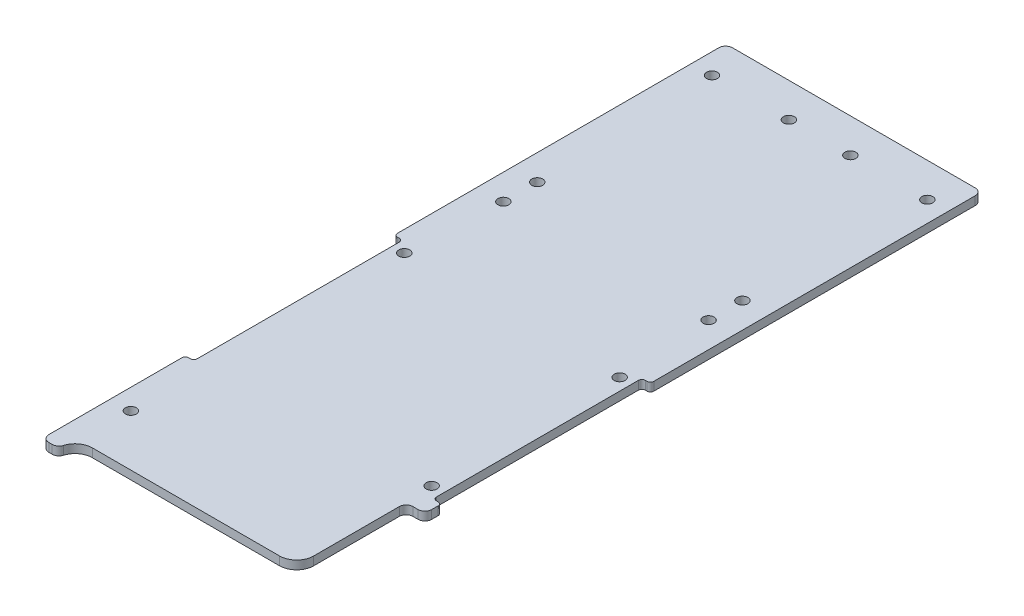
SolidWorks part; units mm, degrees
ref_plane "Front Plane" through (0, 0, 0) normal (0, 0, 1) x (1, 0, 0)
ref_plane "Top Plane" through (0, 0, 0) normal (0, 1, 0) x (1, 0, 0)
ref_plane "Right Plane" through (0, 0, 0) normal (1, 0, 0) x (0, 0, -1)
sketch "Sketch1" plane through (0, 0, 0) normal (0, 1, 0) x (1, 0, 0)
  line L0 (-39.9997, 0) -> (-39.9997, 114.3) construction
  line L1 (-47.625, 127) -> (47.625, 127)
  line L2 (-47.625, 127) -> (-47.625, -127)
  line L3 (-47.625, -127) -> (47.625, -127)
  line L4 (47.625, 127) -> (47.625, -127)
  line L5 (-47.625, 127) -> (47.625, -127) construction
  line L6 (-47.625, -127) -> (47.625, 127) construction
  line L7 (0, 0) -> (0, 127) construction
  line L8 (-39.9997, 0) -> (-39.9997, -101.6) construction
  line L9 (-39.9997, 0) -> (0, 0) construction
  line L10 (-41.275, -127) -> (-41.275, -120.65)
  line L11 (-41.275, -120.65) -> (41.275, -120.65)
  line L12 (41.275, -120.65) -> (41.275, -127)
  line L13 (-39.9997, 114.3) -> (-11.4247, 114.3) construction
  line L14 (39.9997, 114.3) -> (11.4247, 114.3) construction
  circle A0 centre (-39.9997, 114.3) radius 2.032
  circle A1 centre (-39.9997, 0) radius 2.032
  circle A2 centre (-39.9997, -101.6) radius 2.032
  circle A3 centre (39.9997, -101.6) radius 2.032
  circle A4 centre (39.9997, 0) radius 2.032
  circle A5 centre (39.9997, 114.3) radius 2.032
  circle A6 centre (-11.4247, 114.3) radius 2.032
  circle A7 centre (11.4247, 114.3) radius 2.032
  circle A8 centre (-39.9997, -69.85) radius 2.032
  circle A9 centre (39.9997, -69.85) radius 2.032
  point P0 (0, 0)
  dimension "D4" = 4.064
  dimension "D10" = 28.575
  dimension "D1" = 95.25
  dimension "D2" = 254
  dimension "D3" = 7.6253
  dimension "D5" = 12.7
  dimension "D6" = 25.4
  dimension "D7" = 6.35
  dimension "D8" = 6.35
  dimension "D9" = 6.35
  dimension "D11" = 69.85
extrude "Boss-Extrude1" add sketch "Sketch1" along normal blind 3.175 contours L4 L1 L2 L3 A4 A0 A1 A2 A3 A5 | A8 | A3 region at (0, 0, -2.6944) region at (39.9997, 0, 101.6) region at (-39.9997, 0, 69.85)
fillet "Fillet1" radius 2.54 4 edges at (-47.625, 1.5875, -127) (47.625, 1.5875, -127) (47.625, 1.5875, 127) (-47.625, 1.5875, 127)
fillet "Fillet2" radius 2.54 2 edges at (41.275, 1.5875, 127) (-41.275, 1.5875, 127)
fillet "Fillet3" radius 6.35 2 edges at (41.275, 1.5875, 120.65) (-41.275, 1.5875, 120.65)
sketch "Sketch2" plane through (0, 0, 0) normal (0, -1, 0) x (1, 0, 0)
  line L0 (41.9124, 131.8831) -> (41.9124, 109.8659) construction
  line L1 (41.9124, 109.8659) -> (41.9124, 106.3879) construction
  line L2 (41.9124, 83.271) -> (41.9124, 82.5325) construction
  line L3 (41.9124, 82.5325) -> (41.9124, 81.2514) construction
  line L4 (41.9124, 83.271) -> (41.9124, 106.3879) construction
  line L5 (41.9124, 131.8831) -> (41.9124, 109.8659)
  line L6 (41.9124, 109.8659) -> (41.9124, 106.3879)
  line L7 (41.9124, 83.271) -> (41.9124, 82.5325)
  line L8 (41.9124, 82.5325) -> (41.9124, 81.2514)
  line L9 (41.9124, 83.271) -> (41.9124, 106.3879)
  line L10 (41.9124, 81.2514) -> (47.625, 81.2514)
  line L11 (47.625, -124.46) -> (47.625, 124.46) construction
  line L12 (41.9124, 131.8831) -> (47.625, 131.8831)
  line L13 (47.625, 131.8831) -> (47.625, 81.2514)
  line L14 (40.6424, 79.9814) -> (48.895, 79.9814)
  line L15 (48.895, 133.1531) -> (48.895, 79.9814)
  line L16 (40.6424, 133.1531) -> (48.895, 133.1531)
  line L17 (40.6424, 133.1531) -> (40.6424, 109.8659)
  line L18 (40.6424, 109.8659) -> (40.6424, 106.3879)
  line L19 (40.6424, 83.271) -> (40.6424, 106.3879)
  line L20 (40.6424, 83.271) -> (40.6424, 82.5325)
  line L21 (40.6424, 82.5325) -> (40.6424, 79.9814)
  arc M7 (43.815, 127) -> (41.3809, 125.1857) centre (43.815, 124.46) ccw
  arc M8 (41.3809, 125.1857) -> (35.2956, 120.65) centre (35.2956, 127) cw
  line M18 (47.625, -124.46) -> (47.625, 124.46)
  dimension "D1" = 1.27
extrude "Cut-Extrude1" cut sketch "Sketch2" against normal through all contours L20 L21 L14 L10 L8 L7 L9 L19 M18 | L19 L9 L6 L5 L17 L18 M7 M8 | L13 L10 L8 L7 L9 L6 L5 L12 region at (41.6773, 0, 99.982)
fillet "Fillet4" radius 6.35 1 edges at (40.6424, 1.5875, 123.5744)
fillet "Fillet5" radius 2.54 2 edges at (47.625, 1.5875, 79.9814) (40.6424, 1.5875, 79.9814)
sketch "Sketch3" plane through (0, 0, 0) normal (0, -1, 0) x (1, 0, 0)
  line L0 (-36.3082, -49.7791) -> (-39.915, -49.7791) construction
  line L1 (-40.423, -49.276) -> (-40.423, -45.7043) construction
  line L2 (-35.8002, -45.7043) -> (-35.8002, -49.276) construction
  line L3 (-39.915, -45.2013) -> (-36.3082, -45.2013) construction
  line L4 (-36.3082, -37.2027) -> (-39.915, -37.2027) construction
  line L5 (-35.8002, -33.1279) -> (-35.8002, -36.6996) construction
  line L6 (-40.423, -36.6996) -> (-40.423, -33.1279) construction
  line L7 (-39.915, -32.6249) -> (-36.3082, -32.6249) construction
  line L8 (36.285, -32.6249) -> (39.8918, -32.6249) construction
  line L9 (40.3998, -33.1279) -> (40.3998, -36.6996) construction
  line L10 (39.8918, -37.2027) -> (36.285, -37.2027) construction
  line L11 (35.777, -36.6996) -> (35.777, -33.1279) construction
  line L12 (36.285, -45.2013) -> (39.8918, -45.2013) construction
  line L13 (35.777, -49.276) -> (35.777, -45.7043) construction
  line L14 (40.3998, -45.7043) -> (40.3998, -49.276) construction
  line L15 (39.8918, -49.7791) -> (36.285, -49.7791) construction
  line L16 (-36.3082, -49.7791) -> (-39.915, -49.7791)
  line L17 (-40.423, -49.276) -> (-40.423, -45.7043)
  line L18 (-35.8002, -45.7043) -> (-35.8002, -49.276)
  line L19 (-39.915, -45.2013) -> (-36.3082, -45.2013)
  line L20 (-36.3082, -37.2027) -> (-39.915, -37.2027)
  line L21 (-35.8002, -33.1279) -> (-35.8002, -36.6996)
  line L22 (-40.423, -36.6996) -> (-40.423, -33.1279)
  line L23 (-39.915, -32.6249) -> (-36.3082, -32.6249)
  line L24 (36.285, -32.6249) -> (39.8918, -32.6249)
  line L25 (40.3998, -33.1279) -> (40.3998, -36.6996)
  line L26 (39.8918, -37.2027) -> (36.285, -37.2027)
  line L27 (35.777, -36.6996) -> (35.777, -33.1279)
  line L28 (36.285, -45.2013) -> (39.8918, -45.2013)
  line L29 (35.777, -49.276) -> (35.777, -45.7043)
  line L30 (40.3998, -45.7043) -> (40.3998, -49.276)
  line L31 (39.8918, -49.7791) -> (36.285, -49.7791)
  line L32 (-47.625, -25.836) -> (47.625, -25.836)
  line L33 (-47.625, -124.46) -> (-47.625, 124.46) construction
  line L34 (47.625, -124.46) -> (47.625, 77.4414) construction
  line L35 (0, -25.836) -> (0, -56.0686) construction
  line L38 (134.3626, -51.414) -> (184.1384, -51.414)
  line L39 (184.1384, -51.414) -> (184.1384, -43.4909)
  line L40 (184.1384, -43.4909) -> (182.335, -43.4909)
  line L41 (181.827, -42.9878) -> (181.827, -39.4161)
  line L42 (182.335, -38.9131) -> (184.1384, -38.9131)
  line L43 (184.1384, -38.9131) -> (184.1384, -30.9899)
  line L44 (184.1384, -30.9899) -> (134.3626, -30.9899)
  line L45 (134.3626, -30.9899) -> (133.3384, -32.0042)
  line L46 (133.3384, -32.0042) -> (132.3143, -30.9899)
  line L47 (132.3143, -30.9899) -> (70.8626, -30.9899)
  line L48 (70.8626, -30.9899) -> (69.8384, -32.0042)
  line L49 (69.8384, -32.0042) -> (68.8143, -30.9899)
  line L50 (68.8143, -30.9899) -> (7.3626, -30.9899)
  line L51 (7.3626, -30.9899) -> (6.3384, -32.0042)
  line L52 (6.3384, -32.0042) -> (5.3143, -30.9899)
  line L53 (5.3143, -30.9899) -> (-56.1374, -30.9899)
  line L54 (-56.1374, -30.9899) -> (-57.1616, -32.0042)
  line L55 (-57.1616, -32.0042) -> (-58.1857, -30.9899)
  line L56 (-58.1857, -30.9899) -> (-119.6374, -30.9899)
  line L57 (-119.6374, -30.9899) -> (-120.6616, -32.0042)
  line L58 (-120.6616, -32.0042) -> (-121.6857, -30.9899)
  line L59 (-121.6857, -30.9899) -> (-184.1616, -30.9899)
  line L60 (-184.1616, -30.9899) -> (-184.1616, -51.414)
  line L61 (-184.1616, -51.414) -> (-121.6857, -51.414)
  line L62 (-121.6857, -51.414) -> (-120.6616, -50.3998)
  line L63 (-120.6616, -50.3998) -> (-119.6374, -51.414)
  line L64 (-119.6374, -51.414) -> (-58.1857, -51.414)
  line L65 (-58.1857, -51.414) -> (-57.1616, -50.3998)
  line L66 (-57.1616, -50.3998) -> (-56.1374, -51.414)
  line L67 (-56.1374, -51.414) -> (5.3143, -51.414)
  line L68 (5.3143, -51.414) -> (6.3384, -50.3998)
  line L69 (6.3384, -50.3998) -> (7.3626, -51.414)
  line L70 (7.3626, -51.414) -> (68.8143, -51.414)
  line L71 (68.8143, -51.414) -> (69.8384, -50.3998)
  line L72 (69.8384, -50.3998) -> (70.8626, -51.414)
  line L73 (70.8626, -51.414) -> (132.3143, -51.414)
  line L74 (132.3143, -51.414) -> (133.3384, -50.3998)
  line L75 (133.3384, -50.3998) -> (134.3626, -51.414)
  line L76 (134.3626, -51.414) -> (184.1384, -51.414)
  line L77 (184.1384, -51.414) -> (184.1384, -43.4909)
  line L78 (184.1384, -43.4909) -> (182.335, -43.4909)
  line L79 (181.827, -42.9878) -> (181.827, -39.4161)
  line L80 (182.335, -38.9131) -> (184.1384, -38.9131)
  line L81 (184.1384, -38.9131) -> (184.1384, -30.9899)
  line L82 (184.1384, -30.9899) -> (134.3626, -30.9899)
  line L83 (134.3626, -30.9899) -> (133.3384, -32.0042)
  line L84 (133.3384, -32.0042) -> (132.3143, -30.9899)
  line L85 (132.3143, -30.9899) -> (70.8626, -30.9899)
  line L86 (70.8626, -30.9899) -> (69.8384, -32.0042)
  line L87 (69.8384, -32.0042) -> (68.8143, -30.9899)
  line L88 (68.8143, -30.9899) -> (7.3626, -30.9899)
  line L89 (7.3626, -30.9899) -> (6.3384, -32.0042)
  line L90 (6.3384, -32.0042) -> (5.3143, -30.9899)
  line L91 (5.3143, -30.9899) -> (-56.1374, -30.9899)
  line L92 (-56.1374, -30.9899) -> (-57.1616, -32.0042)
  line L93 (-57.1616, -32.0042) -> (-58.1857, -30.9899)
  line L94 (-58.1857, -30.9899) -> (-119.6374, -30.9899)
  line L95 (-119.6374, -30.9899) -> (-120.6616, -32.0042)
  line L96 (-120.6616, -32.0042) -> (-121.6857, -30.9899)
  line L97 (-121.6857, -30.9899) -> (-184.1616, -30.9899)
  line L98 (-184.1616, -30.9899) -> (-184.1616, -51.414)
  line L99 (-184.1616, -51.414) -> (-121.6857, -51.414)
  line L100 (-121.6857, -51.414) -> (-120.6616, -50.3998)
  line L101 (-120.6616, -50.3998) -> (-119.6374, -51.414)
  line L102 (-119.6374, -51.414) -> (-58.1857, -51.414)
  line L103 (-58.1857, -51.414) -> (-57.1616, -50.3998)
  line L104 (-57.1616, -50.3998) -> (-56.1374, -51.414)
  line L105 (-56.1374, -51.414) -> (5.3143, -51.414)
  line L106 (5.3143, -51.414) -> (6.3384, -50.3998)
  line L107 (6.3384, -50.3998) -> (7.3626, -51.414)
  line L108 (7.3626, -51.414) -> (68.8143, -51.414)
  line L109 (68.8143, -51.414) -> (69.8384, -50.3998)
  line L110 (69.8384, -50.3998) -> (70.8626, -51.414)
  line L111 (70.8626, -51.414) -> (132.3143, -51.414)
  line L112 (132.3143, -51.414) -> (133.3384, -50.3998)
  line L113 (133.3384, -50.3998) -> (134.3626, -51.414)
  line L1362 (-40.423, -34.9138) -> (-35.8002, -34.9138)
  line L1857 (-38.1116, -32.6249) -> (-38.1116, -37.2027)
  line L1858 (-38.1116, -45.2013) -> (-38.1116, -49.7791)
  line L1859 (-40.423, -47.4902) -> (-35.8002, -47.4902)
  circle A0 centre (-38.1116, -34.9138) radius 2.032
  circle A1 centre (-38.1116, -47.4902) radius 2.032
  circle A2 centre (38.1116, -47.4902) radius 2.032
  circle A3 centre (38.1116, -34.9138) radius 2.032
  ellipse E0 centre (-39.915, -45.7043) end of major axis (-39.407, -45.7043) minor radius 0.5031 (-39.915, -45.2013) -> (-40.423, -45.7043) ccw construction
  ellipse E1 centre (-39.915, -49.276) end of major axis (-39.407, -49.276) minor radius 0.5031 (-40.423, -49.276) -> (-39.915, -49.7791) ccw construction
  ellipse E2 centre (182.335, -42.9878) end of major axis (182.843, -42.9878) minor radius 0.5031 (181.827, -42.9878) -> (182.335, -43.4909) ccw
  ellipse E3 centre (182.335, -39.4161) end of major axis (182.843, -39.4161) minor radius 0.5031 (182.335, -38.9131) -> (181.827, -39.4161) ccw
  ellipse E4 centre (182.335, -42.9878) end of major axis (182.843, -42.9878) minor radius 0.5031 (181.827, -42.9878) -> (182.335, -43.4909) ccw
  ellipse E5 centre (182.335, -39.4161) end of major axis (182.843, -39.4161) minor radius 0.5031 (182.335, -38.9131) -> (181.827, -39.4161) ccw
  ellipse E6 centre (-36.3082, -49.276) end of major axis (-35.8002, -49.276) minor radius 0.5031 (-36.3082, -49.7791) -> (-35.8002, -49.276) ccw construction
  ellipse E7 centre (-36.3082, -45.7043) end of major axis (-35.8002, -45.7043) minor radius 0.5031 (-35.8002, -45.7043) -> (-36.3082, -45.2013) ccw construction
  ellipse E8 centre (-39.915, -36.6996) end of major axis (-39.407, -36.6996) minor radius 0.5031 (-40.423, -36.6996) -> (-39.915, -37.2027) ccw construction
  ellipse E9 centre (-36.3082, -36.6996) end of major axis (-35.8002, -36.6996) minor radius 0.5031 (-36.3082, -37.2027) -> (-35.8002, -36.6996) ccw construction
  ellipse E10 centre (-36.3082, -33.1279) end of major axis (-35.8002, -33.1279) minor radius 0.5031 (-35.8002, -33.1279) -> (-36.3082, -32.6249) ccw construction
  ellipse E11 centre (-39.915, -33.1279) end of major axis (-39.407, -33.1279) minor radius 0.5031 (-39.915, -32.6249) -> (-40.423, -33.1279) ccw construction
  ellipse E12 centre (39.8918, -33.1279) end of major axis (40.3998, -33.1279) minor radius 0.5031 (40.3998, -33.1279) -> (39.8918, -32.6249) ccw construction
  ellipse E13 centre (36.285, -33.1279) end of major axis (36.793, -33.1279) minor radius 0.5031 (36.285, -32.6249) -> (35.777, -33.1279) ccw construction
  ellipse E14 centre (39.8918, -36.6996) end of major axis (40.3998, -36.6996) minor radius 0.5031 (39.8918, -37.2027) -> (40.3998, -36.6996) ccw construction
  ellipse E15 centre (36.285, -36.6996) end of major axis (36.793, -36.6996) minor radius 0.5031 (35.777, -36.6996) -> (36.285, -37.2027) ccw construction
  ellipse E16 centre (36.285, -45.7043) end of major axis (36.793, -45.7043) minor radius 0.5031 (36.285, -45.2013) -> (35.777, -45.7043) ccw construction
  ellipse E17 centre (36.285, -49.276) end of major axis (36.793, -49.276) minor radius 0.5031 (35.777, -49.276) -> (36.285, -49.7791) ccw construction
  ellipse E18 centre (39.8918, -45.7043) end of major axis (40.3998, -45.7043) minor radius 0.5031 (40.3998, -45.7043) -> (39.8918, -45.2013) ccw construction
  ellipse E19 centre (39.8918, -49.276) end of major axis (40.3998, -49.276) minor radius 0.5031 (39.8918, -49.7791) -> (40.3998, -49.276) ccw construction
  ellipse E20 centre (-39.915, -45.7043) end of major axis (-39.407, -45.7043) minor radius 0.5031 (-39.915, -45.2013) -> (-40.423, -45.7043) ccw
  ellipse E21 centre (-39.915, -49.276) end of major axis (-39.407, -49.276) minor radius 0.5031 (-40.423, -49.276) -> (-39.915, -49.7791) ccw
  ellipse E22 centre (-36.3082, -49.276) end of major axis (-35.8002, -49.276) minor radius 0.5031 (-36.3082, -49.7791) -> (-35.8002, -49.276) ccw
  ellipse E23 centre (-36.3082, -45.7043) end of major axis (-35.8002, -45.7043) minor radius 0.5031 (-35.8002, -45.7043) -> (-36.3082, -45.2013) ccw
  ellipse E24 centre (-39.915, -36.6996) end of major axis (-39.407, -36.6996) minor radius 0.5031 (-40.423, -36.6996) -> (-39.915, -37.2027) ccw
  ellipse E25 centre (-36.3082, -36.6996) end of major axis (-35.8002, -36.6996) minor radius 0.5031 (-36.3082, -37.2027) -> (-35.8002, -36.6996) ccw
  ellipse E26 centre (-36.3082, -33.1279) end of major axis (-35.8002, -33.1279) minor radius 0.5031 (-35.8002, -33.1279) -> (-36.3082, -32.6249) ccw
  ellipse E27 centre (-39.915, -33.1279) end of major axis (-39.407, -33.1279) minor radius 0.5031 (-39.915, -32.6249) -> (-40.423, -33.1279) ccw
  ellipse E28 centre (39.8918, -33.1279) end of major axis (40.3998, -33.1279) minor radius 0.5031 (40.3998, -33.1279) -> (39.8918, -32.6249) ccw
  ellipse E29 centre (36.285, -33.1279) end of major axis (36.793, -33.1279) minor radius 0.5031 (36.285, -32.6249) -> (35.777, -33.1279) ccw
  ellipse E30 centre (39.8918, -36.6996) end of major axis (40.3998, -36.6996) minor radius 0.5031 (39.8918, -37.2027) -> (40.3998, -36.6996) ccw
  ellipse E31 centre (36.285, -36.6996) end of major axis (36.793, -36.6996) minor radius 0.5031 (35.777, -36.6996) -> (36.285, -37.2027) ccw
  ellipse E32 centre (36.285, -45.7043) end of major axis (36.793, -45.7043) minor radius 0.5031 (36.285, -45.2013) -> (35.777, -45.7043) ccw
  ellipse E33 centre (36.285, -49.276) end of major axis (36.793, -49.276) minor radius 0.5031 (35.777, -49.276) -> (36.285, -49.7791) ccw
  ellipse E34 centre (39.8918, -45.7043) end of major axis (40.3998, -45.7043) minor radius 0.5031 (40.3998, -45.7043) -> (39.8918, -45.2013) ccw
  ellipse E35 centre (39.8918, -49.276) end of major axis (40.3998, -49.276) minor radius 0.5031 (39.8918, -49.7791) -> (40.3998, -49.276) ccw
  dimension "D2" = 4.064
  dimension "D1" = 0
extrude "Cut-Extrude2" cut sketch "Sketch3" against normal through all contours A0 | A1 | A2 | A3
sketch "Sketch4" plane through (0, 3.175, 0) normal (0, 1, 0) x (1, 0, 0)
  line L0 (-44.45, 3.81) -> (-46.99, 3.81) construction
  line L1 (-46.99, 3.81) -> (-46.99, 121.92) construction
  line L2 (-42.545, 126.365) -> (-0.635, 126.365) construction
  line L3 (-0.635, 126.365) -> (-0.635, 107.95) construction
  line L4 (-6.35, 102.235) -> (-15.875, 102.235) construction
  line L5 (-22.86, 95.25) -> (-22.86, -115.57) construction
  line L6 (-27.305, -120.015) -> (-35.4551, -120.015) construction
  line L7 (-43.815, -126.365) -> (-45.085, -126.365) construction
  line L8 (-46.99, -124.46) -> (-46.99, -73.7819) construction
  line L9 (-46.99, -73.7819) -> (-44.45, -73.7819) construction
  line L10 (-44.45, -73.7819) -> (-44.45, 3.81) construction
  line L11 (-46.99, 3.81) -> (-44.45, 3.81)
  line L12 (-46.99, 121.92) -> (-46.99, 3.81)
  line L13 (-0.635, 126.365) -> (-42.545, 126.365)
  line L14 (-0.635, 107.95) -> (-0.635, 126.365)
  line L15 (-15.875, 102.235) -> (-6.35, 102.235)
  line L16 (-22.86, -115.57) -> (-22.86, 95.25)
  line L17 (-35.4551, -120.015) -> (-27.305, -120.015)
  line L18 (-45.085, -126.365) -> (-43.815, -126.365)
  line L19 (-46.99, -73.7819) -> (-46.99, -124.46)
  line L20 (-44.45, -73.7819) -> (-46.99, -73.7819)
  line L21 (-44.45, 3.81) -> (-44.45, -73.7819)
  line L22 (-46.99, 3.81) -> (-44.45, 3.81)
  line L23 (-46.99, 121.92) -> (-46.99, 3.81)
  line L24 (-0.635, 126.365) -> (-42.545, 126.365)
  line L25 (-0.635, 107.95) -> (-0.635, 126.365)
  line L26 (-15.875, 102.235) -> (-6.35, 102.235)
  line L27 (-22.86, -115.57) -> (-22.86, 95.25)
  line L28 (-35.4551, -120.015) -> (-27.305, -120.015)
  line L29 (-45.085, -126.365) -> (-43.815, -126.365)
  line L30 (-46.99, -73.7819) -> (-46.99, -124.46)
  line L31 (-44.45, -73.7819) -> (-46.99, -73.7819)
  line L32 (-44.45, 3.81) -> (-44.45, -73.7819)
  line L33 (40.64, -77.5286) -> (40.64, -117.0408) construction
  line L34 (35.4551, -120.015) -> (27.305, -120.015) construction
  line L35 (22.86, -115.57) -> (22.86, 95.25) construction
  line L36 (15.875, 102.235) -> (6.35, 102.235) construction
  line L37 (0.635, 107.95) -> (0.635, 126.365) construction
  line L38 (0.635, 126.365) -> (42.545, 126.365) construction
  line L39 (46.99, 121.92) -> (46.99, 3.81) construction
  line L40 (46.99, 3.81) -> (44.45, 3.81) construction
  line L41 (44.45, 3.81) -> (44.45, -73.7819) construction
  line L42 (44.45, -73.7819) -> (46.99, -73.7819) construction
  line L43 (46.99, -73.7819) -> (46.99, -77.5286) construction
  line L44 (46.99, -77.5286) -> (40.64, -77.5286) construction
  line L45 (-44.45, 3.81) -> (-46.99, 3.81)
  line L46 (-46.99, 3.81) -> (-46.99, 121.92)
  line L47 (-42.545, 126.365) -> (-0.635, 126.365)
  line L48 (-0.635, 126.365) -> (-0.635, 107.95)
  line L49 (-6.35, 102.235) -> (-15.875, 102.235)
  line L50 (-22.86, 95.25) -> (-22.86, -115.57)
  line L51 (-27.305, -120.015) -> (-35.4551, -120.015)
  line L52 (-43.815, -126.365) -> (-45.085, -126.365)
  line L53 (-46.99, -124.46) -> (-46.99, -73.7819)
  line L54 (-46.99, -73.7819) -> (-44.45, -73.7819)
  line L55 (-44.45, -73.7819) -> (-44.45, 3.81)
  line L56 (40.64, -77.5286) -> (40.64, -117.0408)
  line L57 (35.4551, -120.015) -> (27.305, -120.015)
  line L58 (22.86, -115.57) -> (22.86, 95.25)
  line L59 (15.875, 102.235) -> (6.35, 102.235)
  line L60 (0.635, 107.95) -> (0.635, 126.365)
  line L61 (0.635, 126.365) -> (42.545, 126.365)
  line L62 (46.99, 121.92) -> (46.99, 3.81)
  line L63 (46.99, 3.81) -> (44.45, 3.81)
  line L64 (44.45, 3.81) -> (44.45, -73.7819)
  line L65 (44.45, -73.7819) -> (46.99, -73.7819)
  line L66 (46.99, -73.7819) -> (46.99, -77.5286)
  line L67 (46.99, -77.5286) -> (40.64, -77.5286)
  line L178 (-46.99, 3.81) -> (-47.625, 3.81)
  line L179 (-47.625, 124.46) -> (-47.625, -124.46) construction
  line L180 (-46.99, -73.7819) -> (-47.625, -73.7819)
  line L181 (46.99, -73.7819) -> (47.625, -73.7819)
  line L182 (47.625, 124.46) -> (47.625, -77.4414) construction
  line L183 (46.99, 3.81) -> (47.625, 3.81)
  arc A0 (-42.545, 126.365) -> (-46.99, 121.92) centre (-42.545, 121.92) ccw construction
  arc A1 (-6.35, 102.235) -> (-0.635, 107.95) centre (-6.35, 107.95) ccw construction
  arc A2 (-15.875, 102.235) -> (-22.86, 95.25) centre (-15.875, 95.25) ccw construction
  arc A3 (-27.305, -120.015) -> (-22.86, -115.57) centre (-27.305, -115.57) ccw construction
  arc A4 (-35.4551, -120.015) -> (-41.9138, -124.3399) centre (-35.4551, -127) ccw construction
  arc A5 (-43.815, -126.365) -> (-41.9138, -124.3399) centre (-43.815, -124.46) ccw construction
  arc A6 (-46.99, -124.46) -> (-45.085, -126.365) centre (-45.085, -124.46) ccw construction
  arc A7 (-42.545, 126.365) -> (-46.99, 121.92) centre (-42.545, 121.92) ccw
  arc A8 (-6.35, 102.235) -> (-0.635, 107.95) centre (-6.35, 107.95) ccw
  arc A9 (-15.875, 102.235) -> (-22.86, 95.25) centre (-15.875, 95.25) ccw
  arc A10 (-27.305, -120.015) -> (-22.86, -115.57) centre (-27.305, -115.57) ccw
  arc A11 (-35.4551, -120.015) -> (-41.9138, -124.3399) centre (-35.4551, -127) ccw
  arc A12 (-43.815, -126.365) -> (-41.9138, -124.3399) centre (-43.815, -124.46) ccw
  arc A13 (-46.99, -124.46) -> (-45.085, -126.365) centre (-45.085, -124.46) ccw
  arc A14 (-42.545, 126.365) -> (-46.99, 121.92) centre (-42.545, 121.92) ccw
  arc A15 (-6.35, 102.235) -> (-0.635, 107.95) centre (-6.35, 107.95) ccw
  arc A16 (-15.875, 102.235) -> (-22.86, 95.25) centre (-15.875, 95.25) ccw
  arc A17 (-27.305, -120.015) -> (-22.86, -115.57) centre (-27.305, -115.57) ccw
  arc A18 (-35.4551, -120.015) -> (-41.9138, -124.3399) centre (-35.4551, -127) ccw
  arc A19 (-43.815, -126.365) -> (-41.9138, -124.3399) centre (-43.815, -124.46) ccw
  arc A20 (-46.99, -124.46) -> (-45.085, -126.365) centre (-45.085, -124.46) ccw
  arc A21 (36.8369, -120.153) -> (40.64, -117.0408) centre (37.465, -117.0408) ccw construction
  arc A22 (36.8369, -120.153) -> (35.4551, -120.015) centre (35.4551, -127) ccw construction
  arc A23 (22.86, -115.57) -> (27.305, -120.015) centre (27.305, -115.57) ccw construction
  arc A24 (22.86, 95.25) -> (15.875, 102.235) centre (15.875, 95.25) ccw construction
  arc A25 (0.635, 107.95) -> (6.35, 102.235) centre (6.35, 107.95) ccw construction
  arc A26 (46.99, 121.92) -> (42.545, 126.365) centre (42.545, 121.92) ccw construction
  arc A27 (-42.545, 126.365) -> (-46.99, 121.92) centre (-42.545, 121.92) ccw
  arc A28 (-6.35, 102.235) -> (-0.635, 107.95) centre (-6.35, 107.95) ccw
  arc A29 (-15.875, 102.235) -> (-22.86, 95.25) centre (-15.875, 95.25) ccw
  arc A30 (-27.305, -120.015) -> (-22.86, -115.57) centre (-27.305, -115.57) ccw
  arc A31 (-35.4551, -120.015) -> (-41.9138, -124.3399) centre (-35.4551, -127) ccw
  arc A32 (-43.815, -126.365) -> (-41.9138, -124.3399) centre (-43.815, -124.46) ccw
  arc A33 (-46.99, -124.46) -> (-45.085, -126.365) centre (-45.085, -124.46) ccw
  arc A34 (36.8369, -120.153) -> (40.64, -117.0408) centre (37.465, -117.0408) ccw
  arc A35 (36.8369, -120.153) -> (35.4551, -120.015) centre (35.4551, -127) ccw
  arc A36 (22.86, -115.57) -> (27.305, -120.015) centre (27.305, -115.57) ccw
  arc A37 (22.86, 95.25) -> (15.875, 102.235) centre (15.875, 95.25) ccw
  arc A38 (0.635, 107.95) -> (6.35, 102.235) centre (6.35, 107.95) ccw
  arc A39 (46.99, 121.92) -> (42.545, 126.365) centre (42.545, 121.92) ccw
  line M32 (47.625, -77.4414) -> (47.625, 124.46)
  line M36 (-47.625, 124.46) -> (-47.625, -124.46)
  dimension "D1" = 0
extrude "Cut-Extrude3" cut sketch "Sketch4" against normal through all and the other way through all contours L180 L31 L32 L22 L178 M36 | L183 L63 L64 L65 L181 M32 region at (-46.0375, 3.175, 34.9859) region at (46.0375, 3.175, 34.9859)
fillet "Fillet6" radius 1.27 8 edges at (-44.45, 1.5875, -3.81) (-44.45, 1.5875, 73.7819) (44.45, 1.5875, -3.81) (44.45, 1.5875, 73.7819) (47.625, 1.5875, 73.7819) (47.625, 1.5875, -3.81) (-47.625, 1.5875, 73.7819) (-47.625, 1.5875, -3.81)
